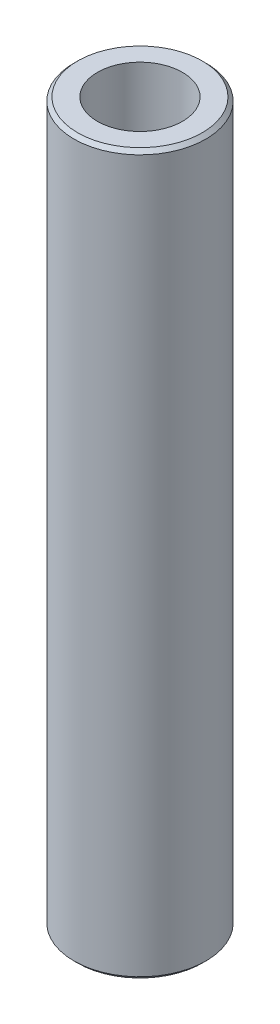
SolidWorks part; units mm, degrees
ref_plane "Front Plane" through (0, 0, 0) normal (0, 0, 1) x (1, 0, 0)
ref_plane "Top Plane" through (0, 0, 0) normal (0, 1, 0) x (1, 0, 0)
ref_plane "Right Plane" through (0, 0, 0) normal (1, 0, 0) x (0, 0, -1)
sketch "Sketch1" plane through (0, 0, 0) normal (0, 1, 0) x (1, 0, 0)
  circle A0 centre (0, 0) radius 55
  dimension "SHAFT_OD" = 110
extrude "Boss-Extrude1" add sketch "Sketch1" along normal blind 600
sketch "Sketch2" plane through (0, 0, 0) normal (0, 1, 0) x (1, 0, 0)
  circle A0 centre (0, 0) radius 35.4764
  dimension "BORE_D" = 70.9527
extrude "Cut-Extrude1" cut sketch "Sketch2" along normal through all
chamfer "Chamfer1" distance 3.0452 angle 45 2 edges at (0, 600, 55) (0, 0, 55)
